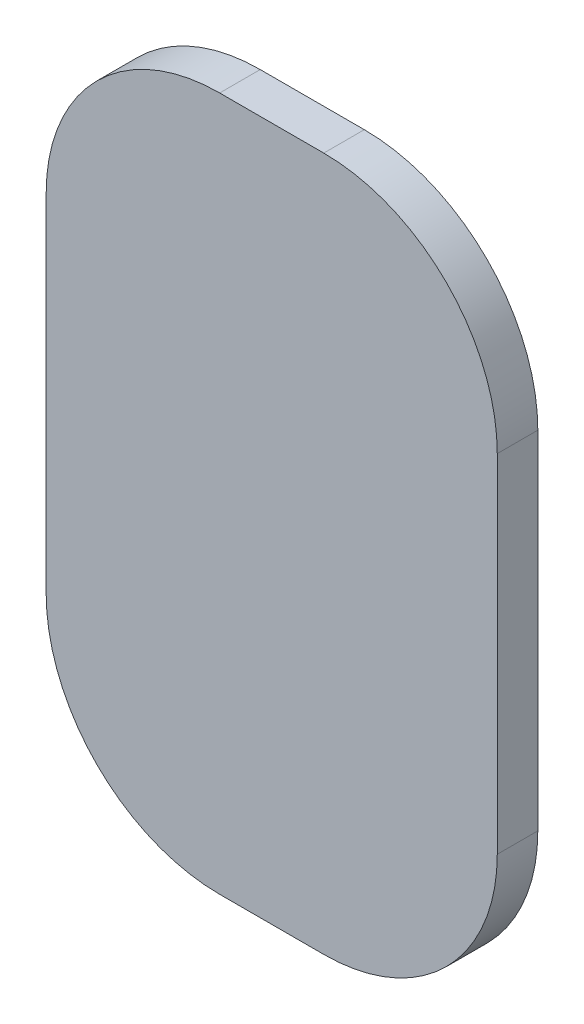
SolidWorks part; units mm, degrees
note: The reader was unsure of these and kept them because the rebuilt part matched: thickness of "Base-Flange1", "Sheet-Metal1".
ref_plane "Front Plane" through (0, 0, 0) normal (0, 0, 1) x (1, 0, 0)
ref_plane "Top Plane" through (0, 0, 0) normal (0, 1, 0) x (1, 0, 0)
ref_plane "Right Plane" through (0, 0, 0) normal (1, 0, 0) x (0, 0, -1)
sketch "Sketch1" plane through (0, 0, 0) normal (0, 0, 1) x (1, 0, 0)
  line L1 (0, 0) -> (13, 0)
  line L2 (0, 0) -> (0, 20)
  line L3 (0, 20) -> (13, 20)
  line L4 (13, 0) -> (13, 20)
  dimension "D1" = 13
  dimension "D2" = 20
base flange "Base-Flange1" sketch "Sketch1" thickness 1.1684 reverse thickness direction no parameters "D1"=1.75
fillet "Fillet1" radius 5 4 edges at (0, 20, -0.5842) (0, 0, -0.5842) (13, 0, -0.5842) (13, 20, -0.5842)
sketch "Bend-Lines1" [suppressed] plane through (0, 0, 0) normal (0, 1, 0) x (1, 0, 0)
sketch "Bounding-Box1" [suppressed] plane through (0, 0, 0) normal (0, 1, 0) x (1, 0, 0)
sheet metal parameters "Sheet-Metal1" thickness 1.1684 parameters "D1"=1.75, "D7"=1.016
flat pattern "Flat-Pattern1" [suppressed]
sketch "Bend-Lines2" plane through (0, 0, 0) normal (0, 1, 0) x (1, 0, 0)
sketch3d "Bounding-Box2" [suppressed]
  line L0 (13, 0, 0) -> (13, 20, 0) construction
  line L1 (0, 0, 0) -> (0, 20, 0) construction
  line L2 (13, 0, 0) -> (0, 0, 0) construction
  line L3 (13, 20, 0) -> (0, 20, 0) construction
